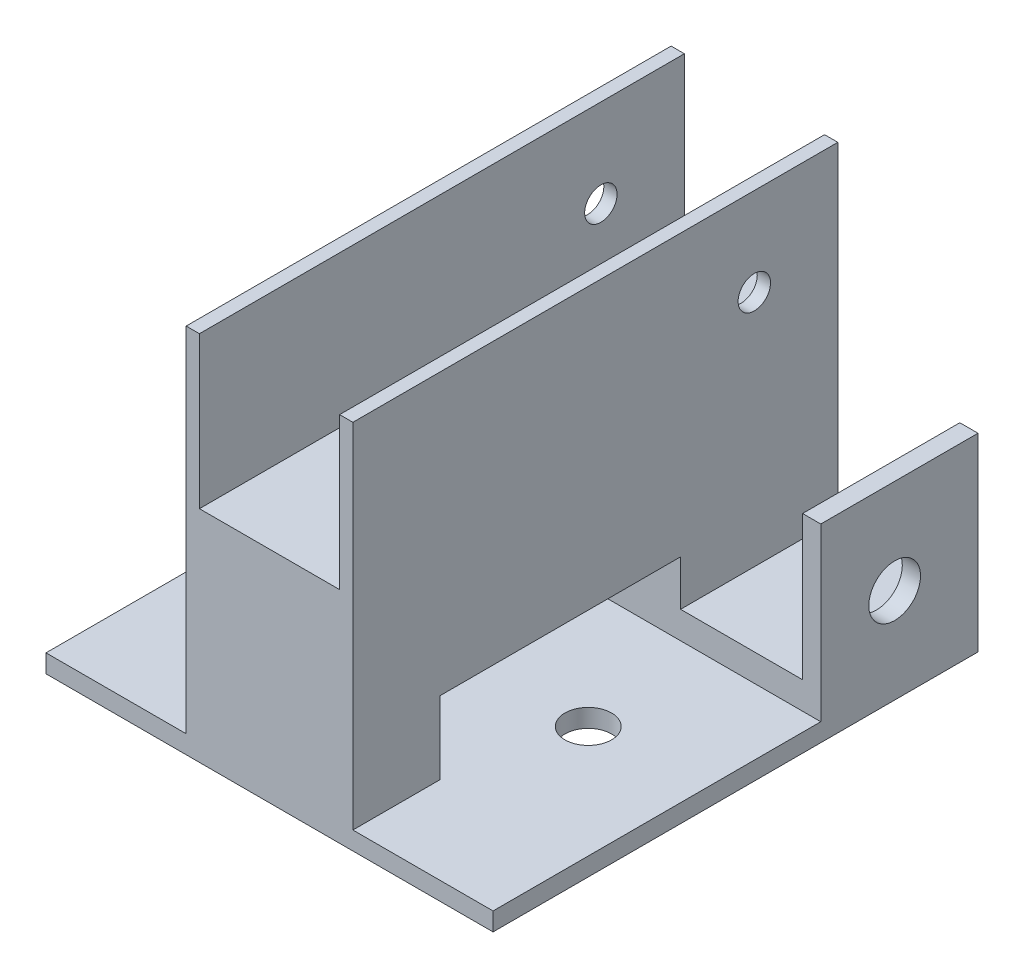
SolidWorks part; units mm, degrees
ref_plane "Front Plane" through (0, 0, 0) normal (0, 0, 1) x (1, 0, 0)
ref_plane "Top Plane" through (0, 0, 0) normal (0, 1, 0) x (1, 0, 0)
ref_plane "Right Plane" through (0, 0, 0) normal (1, 0, 0) x (0, 0, -1)
sketch "Sketch1" plane through (0, 0, 0) normal (0, 1, 0) x (1, 0, 0)
  line L1 (11, -32) -> (-11, -32)
  line L2 (11, -32) -> (11, 32)
  line L3 (11, 32) -> (-11, 32)
  line L4 (-11, -32) -> (-11, 32)
  line L5 (11, -32) -> (-11, 32) construction
  line L6 (11, 32) -> (-11, -32) construction
  point P0 (0, 0)
  dimension "D1" = 22
  dimension "D2" = 64
extrude "Boss-Extrude2" add sketch "Sketch1" along normal blind 49
sketch "Sketch3" plane through (0, 49, 0) normal (0, 1, 0) x (1, 0, 0)
  line L0 (-11, -32) -> (11, -32) construction
  line L1 (-9.25, 32) -> (9.25, 32)
  line L2 (-9.25, 32) -> (-9.25, -32)
  line L3 (-9.25, -32) -> (9.25, -32)
  line L4 (9.25, 32) -> (9.25, -32)
  line L5 (-9.25, 32) -> (9.25, -32) construction
  line L6 (-9.25, -32) -> (9.25, 32) construction
  point P0 (0, 0)
  dimension "D1" = 18.5
extrude "Cut-Extrude1" cut sketch "Sketch3" against normal blind 20
sketch "Sketch4" plane through (11, 0, 0) normal (1, 0, 0) x (0, 0, -1)
  line L0 (32, 49) -> (32, 0) construction
  circle A0 centre (20.979, 37.382) radius 2.14
  dimension "D1" = 4.28
  dimension "D2" = 11.021
  dimension "D4" = 8.382
extrude "Cut-Extrude2" cut sketch "Sketch4" against normal blind 28
sketch "Sketch5" plane through (11, 0, 0) normal (1, 0, 0) x (0, 0, -1)
  line L0 (-32, 49) -> (-32, 0) construction
  line L1 (-32, 6) -> (32, 6)
  line L2 (-32, 6) -> (-32, 0)
  line L3 (-32, 0) -> (32, 0)
  line L4 (32, 6) -> (32, 0)
  dimension "D1" = 6
extrude "Boss-Extrude3" add sketch "Sketch5" along normal blind 18.5
sketch "Sketch6" plane through (0, 6, 0) normal (0, 1, 0) x (1, 0, 0)
  line L0 (29.5, 32) -> (11, 32) construction
  line L1 (27.1, 32) -> (29.5, 32)
  line L2 (27.1, 32) -> (27.1, -32)
  line L3 (27.1, -32) -> (29.5, -32)
  line L4 (29.5, 32) -> (29.5, -32)
  line L5 (29.5, -32) -> (11, -32) construction
  line L6 (29.5, 32) -> (29.5, -32) construction
  dimension "D1" = 2.4
extrude "Boss-Extrude4" add sketch "Sketch6" along normal blind 19
sketch "Sketch7" plane through (29.5, 0, 0) normal (1, 0, 0) x (0, 0, -1)
  line L0 (32, 0) -> (32, 25) construction
  line L2 (-32, 0) -> (32, 0) construction
  circle A0 centre (21, 12.5) radius 3.41
  dimension "D1" = 6.82
  dimension "D2" = 11
  dimension "D4" = 12.5
extrude "Cut-Extrude3" cut sketch "Sketch7" against normal blind 13
sketch "Sketch8" plane through (-11, 0, 0) normal (-1, 0, 0) x (0, 0, 1)
  line L0 (-32, 49) -> (-32, 0) construction
  line L1 (-32, 6) -> (32, 6)
  line L2 (-32, 6) -> (-32, 0)
  line L3 (-32, 0) -> (32, 0)
  line L4 (32, 6) -> (32, 0)
  dimension "D1" = 6
extrude "Boss-Extrude5" add sketch "Sketch8" along normal blind 18.5
sketch "Sketch9" plane through (0, 6, 0) normal (0, 1, 0) x (1, 0, 0)
  line L0 (-29.5, -32) -> (-11, -32) construction
  line L1 (-29.5, 32) -> (-27.1, 32)
  line L2 (-29.5, 32) -> (-29.5, -32)
  line L3 (-29.5, -32) -> (-27.1, -32)
  line L4 (-27.1, 32) -> (-27.1, -32)
  dimension "D1" = 2.4
extrude "Boss-Extrude6" add sketch "Sketch9" along normal blind 19
sketch "Sketch10" plane through (-29.5, 0, 0) normal (-1, 0, 0) x (0, 0, 1)
  line L1 (-32, 25) -> (-32, 0) construction
  line L2 (-32, 0) -> (32, 0) construction
  circle A0 centre (-21, 12.5) radius 3.41
  dimension "D1" = 6.82
  dimension "D3" = 11
  dimension "D4" = 12.5
extrude "Cut-Extrude4" cut sketch "Sketch10" against normal blind 13.5505
sketch "Sketch12" plane through (0, 0, 0) normal (0, -1, 0) x (-1, 0, 0)
  circle A0 centre (14.6918, -4.6286) radius 3.076
  circle A1 centre (-14.6918, -4.6286) radius 3.076
extrude "Cut-Extrude6" cut sketch "Sketch12" against normal through all
sketch "Sketch13" plane through (-11, 0, 0) normal (-1, 0, 0) x (0, 0, 1)
  line L0 (32, 6) -> (-32, 6) construction
  line L1 (-11.25, 6) -> (20.5, 6)
  line L2 (-11.25, 6) -> (-11.25, 12)
  line L3 (-11.25, 12) -> (20.5, 12)
  line L4 (20.5, 6) -> (20.5, 12)
  line L5 (32, 49) -> (32, 6) construction
  dimension "D1" = 31.75
  dimension "D2" = 6
  dimension "D3" = 11.5
extrude "Cut-Extrude7" cut sketch "Sketch13" against normal up to next
sketch "Sketch15" plane through (0, 25, 0) normal (0, 1, 0) x (1, 0, 0)
  line L0 (-27.1, -32) -> (-27.1, 32) construction
  line L1 (-27.1, 11.25) -> (-29.5, 11.25)
  line L2 (-27.1, 11.25) -> (-27.1, -32)
  line L3 (-27.1, -32) -> (-29.5, -32)
  line L4 (-29.5, 11.25) -> (-29.5, -32)
  line L5 (11, 11.25) -> (-11, 11.25) construction
extrude "Cut-Extrude8" cut sketch "Sketch15" against normal blind 19
sketch "Sketch16" plane through (0, 25, 0) normal (0, 1, 0) x (1, 0, 0)
  line L0 (29.5, -32) -> (29.5, 32) construction
  line L1 (29.5, 11.25) -> (27.1, 11.25)
  line L2 (29.5, 11.25) -> (29.5, -32)
  line L3 (29.5, -32) -> (27.1, -32)
  line L4 (27.1, 11.25) -> (27.1, -32)
  line L5 (11, 11.25) -> (-11, 11.25) construction
extrude "Cut-Extrude9" cut sketch "Sketch16" against normal blind 19
sketch "Sketch17" plane through (0, 6, 0) normal (0, 1, 0) x (1, 0, 0)
  line L0 (29.5, -32) -> (29.5, 11.25) construction
  line L1 (-29.5, 11.25) -> (29.5, 11.25)
  line L2 (-29.5, 11.25) -> (-29.5, -20.5)
  line L3 (-29.5, -20.5) -> (29.5, -20.5)
  line L4 (29.5, 11.25) -> (29.5, -20.5)
  line L5 (11, -20.5) -> (-11, -20.5) construction
  line L7 (-29.5, -20.5) -> (-11, -20.5)
  line L8 (-29.5, -20.5) -> (-29.5, -32)
  line L9 (-29.5, -32) -> (-11, -32)
  line L10 (-11, -20.5) -> (-11, -32)
  line L11 (29.5, -20.5) -> (11, -20.5)
  line L12 (29.5, -20.5) -> (29.5, -32)
  line L13 (29.5, -32) -> (11, -32)
  line L14 (11, -20.5) -> (11, -32)
  circle M9 centre (14.6918, -4.6286) radius 3.076
  line M13 (11, 11.25) -> (-11, 11.25)
  line M17 (-27.1, 11.25) -> (-29.5, 11.25)
  line M18 (-29.5, 11.25) -> (-29.5, -32)
  line M19 (-29.5, -32) -> (-11, -32)
  line M20 (-11, -32) -> (-11, -20.5)
  line M21 (-11, -20.5) -> (11, -20.5)
  line M22 (11, -20.5) -> (11, -32)
  line M23 (11, -32) -> (29.5, -32)
  line M24 (29.5, -32) -> (29.5, 11.25)
  line M25 (29.5, 11.25) -> (27.1, 11.25)
  circle M26 centre (-14.6918, -4.6286) radius 3.076
extrude "Cut-Extrude10" cut sketch "Sketch17" against normal blind 3.6 contours L3 L1 M18 M21 M24 M25 M13 M17 M26 M9 | L3 M18 M19 M20 | L3 M22 M23 M24 region at (0, 6, 4.6249) region at (-20.25, 6, 26.25) region at (20.25, 6, 26.25)
